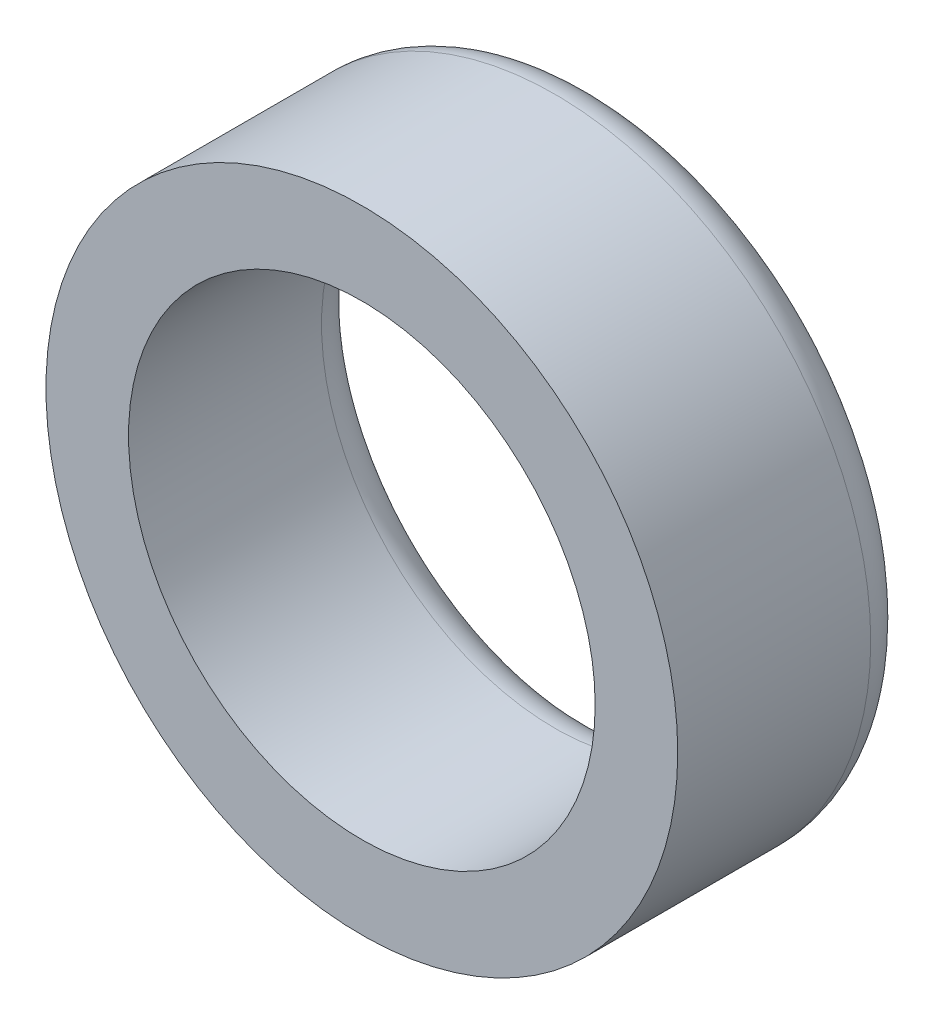
SolidWorks part; units mm, degrees
material "0.6010 (EN-GJL-100)"
ref_plane "Alzado" through (0, 0, 0) normal (0, 0, 1) x (1, 0, 0)
ref_plane "Planta" through (0, 0, 0) normal (0, 1, 0) x (1, 0, 0)
ref_plane "Vista lateral" through (0, 0, 0) normal (1, 0, 0) x (0, 0, -1)
sketch "Croquis2" plane through (0, 0, 0) normal (0, 0, 1) x (1, 0, 0)
  circle A0 centre (0, 0) radius 8.225
  circle A1 centre (0, 0) radius 6.075
  dimension "D1" = 16.45
  dimension "D2" = 2.15
extrude "Saliente-Extruir1" add sketch "Croquis2" against normal blind 6.1
fillet "Redondeo1" 2 edges at (8.225, 0, -6.1) (6.075, 0, -6.1) type full round first side face at (8.225, 0, -6.1) second side face at (6.075, 0, -6.1) middle face at (6.075, 0, -6.1)
